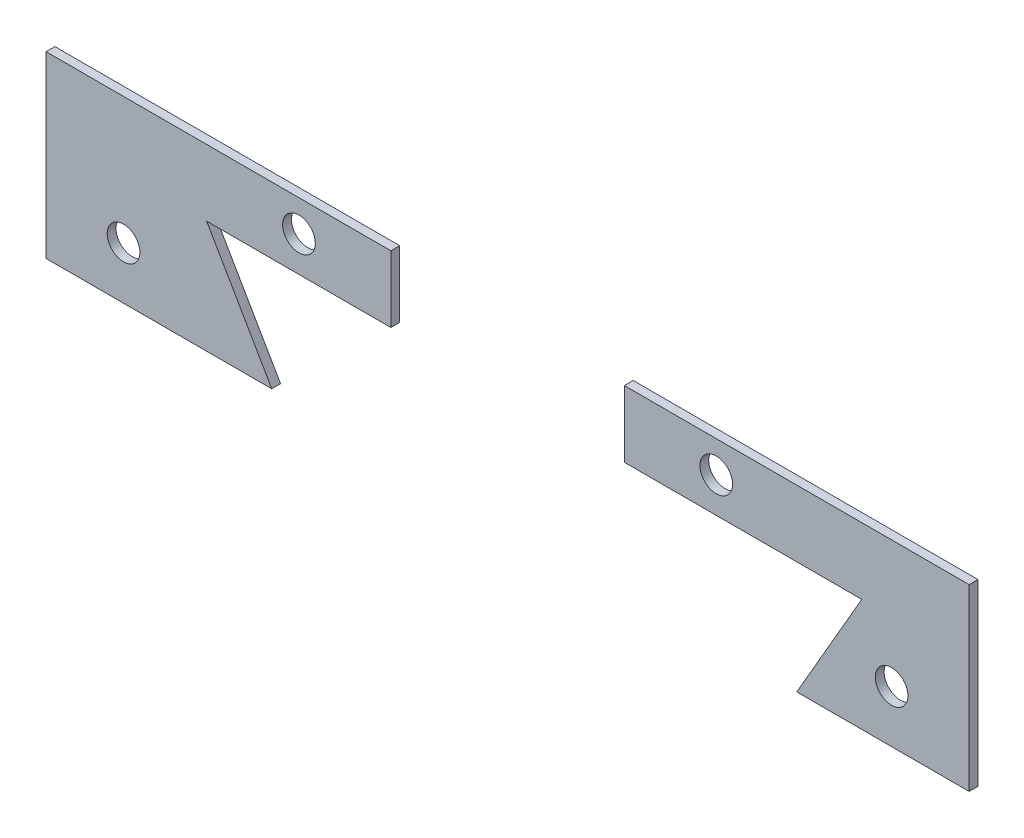
SolidWorks part; units mm, degrees
material "Plain Carbon Steel"
ref_plane "Front Plane" through (0, 0, 0) normal (0, 0, 1) x (1, 0, 0)
ref_plane "Top Plane" through (0, 0, 0) normal (0, 1, 0) x (1, 0, 0)
ref_plane "Right Plane" through (0, 0, 0) normal (1, 0, 0) x (0, 0, -1)
sketch "Sketch4" plane through (0, 0, 0) normal (0, 0, 1) x (1, 0, 0)
  point P0 (0, 0)
  line B0 (-63.5, -15.875) -> (63.5, -15.875)
  line B1 (63.5, -15.875) -> (63.5, 0)
  line B2 (63.5, 0) -> (38.4596, 0)
  line B3 (38.4596, 0) -> (47.625, 15.875)
  line B4 (47.625, 15.875) -> (16.0563, 15.875)
  line B5 (-40.2927, 15.875) -> (-31.1272, 0)
  line B6 (-31.1272, 0) -> (-63.5, 0)
  line B7 (-38.4596, 0) -> (-47.625, 15.875)
  line B8 (-16.0563, -3.175) -> (16.0563, -3.175)
  line B9 (16.0563, -3.175) -> (16.0563, 15.875)
  line B10 (-16.0563, 15.875) -> (-40.2927, 15.875)
  line B11 (-63.5, 0) -> (-63.5, 31.75)
  line B12 (-63.5, 31.75) -> (63.5, 31.75)
  line B13 (63.5, 31.75) -> (63.5, 0)
  line B14 (-16.0563, 15.875) -> (16.0563, 15.875)
  line B15 (-38.4596, 0) -> (38.4596, 0) construction
  line B16 (-28.702, 21.082) -> (28.702, 21.082) construction
  line B17 (-52.832, 7.9375) -> (52.832, 7.9375) construction
  circle B18 centre (0, 6.35) radius 18.669 construction
sketch_block_instance "dovetail pair-1"
sketch_block "dovetail pair" parameters "D8"=37.338, "D1"=60, "D2"=127, "D3"=6.35, "D4"=15.875, "D5"=31.75, "D6"=95.25, "D7"=19.05, "D9"=60, "D10"=31.75, "D11"=50.8, "D12"=23.876, "D13"=7.874, "D14"=10.668, "D15"=34.798, "D16"=21.082, "D17"=7.9375
sketch "Sketch1" plane through (0, 0, 0) normal (0, 0, 1) x (1, 0, 0)
  line L0 (-63.5, 31.75) -> (63.5, 31.75) construction
  line L1 (-63.5, 0) -> (-63.5, 31.75) construction
  line L2 (-31.1272, 0) -> (-63.5, 0) construction
  line L3 (-40.2927, 15.875) -> (-31.1272, 0) construction
  line L4 (-16.0563, 15.875) -> (-40.2927, 15.875) construction
  line L5 (-16.0563, 15.875) -> (16.0563, 15.875) construction
  line L6 (47.625, 15.875) -> (16.0563, 15.875) construction
  line L7 (38.4596, 0) -> (47.625, 15.875) construction
  line L8 (63.5, 0) -> (38.4596, 0) construction
  line L9 (63.5, 31.75) -> (63.5, 0) construction
  line L10 (-63.5, 31.75) -> (63.5, 31.75) construction
  line L11 (-63.5, 0) -> (-63.5, 31.75) construction
  line L12 (-63.5, 0.762) -> (-32.447, 0.762)
  line L13 (-32.447, 0.762) -> (-41.3925, 16.256)
  line L14 (16.0563, 15.875) -> (16.0563, 16.256) construction
  line L15 (-41.3925, 16.256) -> (-16.0563, 16.256)
  line L16 (-16.0563, 16.256) -> (-16.0563, 25.4)
  line L17 (-16.0563, 25.4) -> (-63.5, 25.4)
  line L18 (-31.1272, 0) -> (-63.5, 0) construction
  line L19 (-63.5, 25.4) -> (-63.5, 0.762)
  line L21 (-40.2927, 15.875) -> (-31.1272, 0) construction
  line L24 (-16.0563, 15.875) -> (-16.0563, 16.256) construction
  line L25 (16.0563, 16.256) -> (48.7249, 16.256)
  line L26 (48.7249, 16.256) -> (39.7794, 0.762)
  line L27 (39.7794, 0.762) -> (63.5, 0.762)
  line L28 (63.5, 0.762) -> (63.5, 25.4)
  line L30 (63.5, 25.4) -> (16.0563, 25.4)
  line L33 (-16.0563, 15.875) -> (-40.2927, 15.875) construction
  line L34 (-16.0563, 15.875) -> (16.0563, 15.875) construction
  line L35 (47.625, 15.875) -> (16.0563, 15.875) construction
  line L36 (38.4596, 0) -> (47.625, 15.875) construction
  line L37 (63.5, 0) -> (38.4596, 0) construction
  line L38 (63.5, 31.75) -> (63.5, 0) construction
  line L39 (16.0563, 25.4) -> (16.0563, 16.256)
  dimension "D1" = 25.4
  dimension "D2" = 0.762
  dimension "D3" = 0.762
  dimension "D4" = 0.762
  dimension "D5" = 0.762
extrude "Boss-Extrude1" add sketch "Sketch1" along normal blind 1.2141
hole_wizard "#8 Clearance Hole1" positions "Sketch2" profile "Sketch3" hole size "#8" standard "ANSI Inch" end condition through all
sketch "Sketch2" plane through (0, -15.875, 1.2141) normal (0, 0, 1) x (1, 0, 0)
  point P32 (-28.702, 36.957)
  point P34 (-52.832, 23.8125)
  point P36 (28.702, 36.957)
  point P38 (52.832, 23.8125)
sketch "Sketch3" plane through (-28.702, 21.082, 1.2141) normal (1, 0, 0) x (0, -1, 0)
  line L0 (0, 0) -> (0, 1.2141)
  line L1 (0, 1.2141) -> (2.2479, 1.2141)
  line L2 (2.2479, 1.2141) -> (2.2479, 0)
  line L3 (2.2479, 0) -> (0, 0)
  line L4 (0, -6.35) -> (0, 107.95) construction
  dimension "Thru Hole Dia." = 4.4958
  dimension "Thru Hole Depth" = 1.2141
equation "\"dovetail-angle\" = 60"
equation "\"dovetail-stock-width\" = 5"
equation "\"dovetail-stock-height\" = 1.25"
equation "\"dovetail-depth\" = 0.5 * \"dovetail-stock-height\""
equation "\"dovetail-throat-width\" = \"dovetail-stock-width\" - (2 * \"dovetail-depth\")"
equation "\"delta-x\" = 6"
equation "\"delta-y\" = 3"
equation "\"gib-thickness\" = 0.25"
equation "\"x-slide-length\" = \"dovetail-stock-width\" + \"delta-x\""
equation "\"y-slide-length\" = \"dovetail-stock-width\" + \"delta-y\""
equation "\"dog-point-diam\" = .149"
equation "\"dog-point-length\" = .067"
equation "\"dovetail-double-height\" = 2 * \"dovetail-depth\" + 0.5"
equation "\"acme-major-diam\" = .5"
equation "\"acme-pitch-diam\" = 0.45"
equation "\"acme-minor-diam\" = 0.4"
equation "\"acme-nut-od\" = 1.47"
equation "\"acme-nut-length\" = 1"
equation "\"acme-nut-trim-height\" = .75"
equation "\"screw-bearing-od\" = 0.5"
equation "\"screw-bearing-length\" = .375"
equation "\"screw-bearing-id\" = .3125"
equation "\"end-plate-thickness\" = \"screw-bearing-length\""
equation "\"screw-add-length\" = 2 * \"end-plate-thickness\" + 1 + 0.5"
equation "\"x-screw-length\" = \"x-slide-length\" + \"screw-add-length\""
equation "\"y-screw-length\" = \"y-slide-length\" + \"screw-add-length\""
equation "\"acme-nut-mount-hole-space-horz\" = 0.95"
equation "\"acme-nut-mount-hole-space-vert\" = 0.5 * \"acme-nut-length\""
equation "\"vise-hole-center-dist\" = 6.75"
equation "\"wiper_plate_clearance\" = .03"
equation "\"D2@Sketch1\"=\"wiper_plate_clearance\""
equation "\"D3@Sketch1\"=\"wiper_plate_clearance\""
equation "\"D4@Sketch1\"=\"wiper_plate_clearance\""
equation "\"D5@Sketch1\"=\"wiper_plate_clearance\""
equation "\"D2@dovetail pair\"=\"dovetail-stock-width\""
equation "\"D1@dovetail pair\"=\"dovetail-angle\""
equation "\"D3@dovetail pair\"=\"gib-thickness\""
equation "\"D4@dovetail pair\"=\"dovetail-depth\""
equation "\"D5@dovetail pair\"=\"dovetail-stock-height\""
equation "\"D6@dovetail pair\"=\"dovetail-throat-width\""
equation "\"D10@dovetail pair\"=\"dovetail-stock-height\""
equation "\"D7@dovetail pair\"=\"acme-nut-trim-height\""
equation "\"D8@dovetail pair\"=\"acme-nut-od\""
equation "\"D9@dovetail pair\"=\"dovetail-angle\""
equation "\"D17@dovetail pair\"=\"dovetail-depth\"/2"
